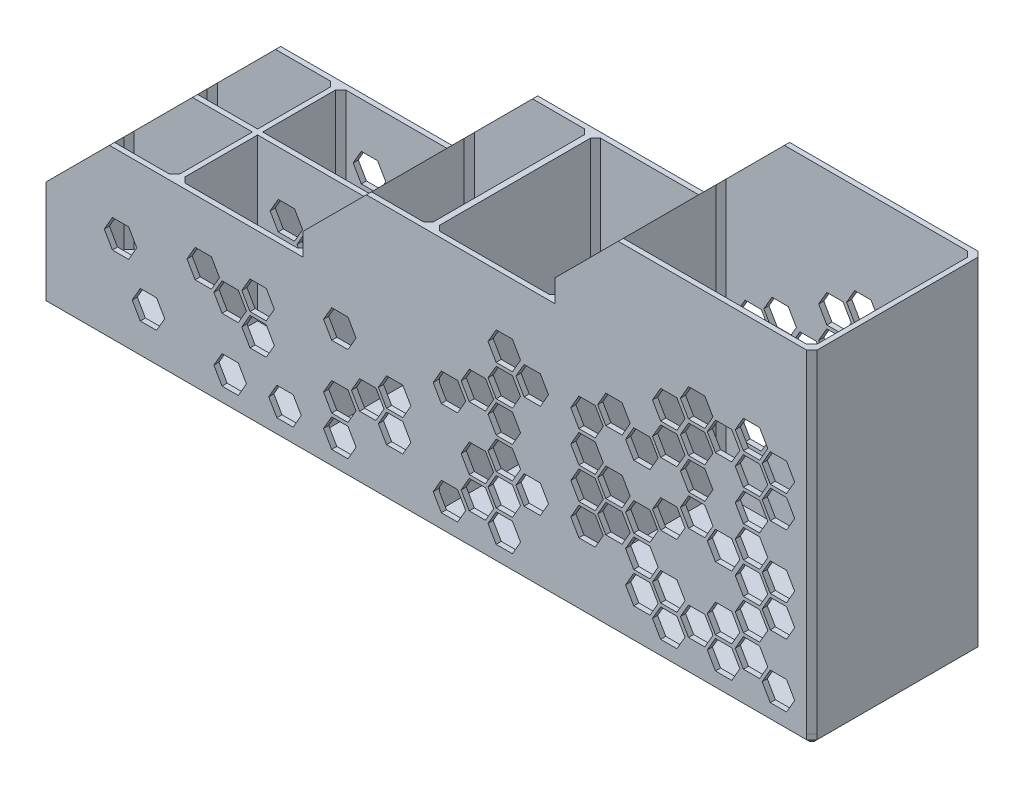
SolidWorks part; units mm, degrees
ref_plane "Front Plane" through (0, 0, 0) normal (0, 0, 1) x (1, 0, 0)
ref_plane "Top Plane" through (0, 0, 0) normal (0, 1, 0) x (1, 0, 0)
ref_plane "Right Plane" through (0, 0, 0) normal (1, 0, 0) x (0, 0, -1)
sketch "Sketch2" plane through (0, 0, 0) normal (0, 1, 0) x (1, 0, 0)
  line L0 (-36, -23.5) -> (36, -23.5)
  line L1 (-111, 25) -> (111, 25)
  line L2 (-112.5, 23.5) -> (-112.5, -23.5)
  line L3 (-111, -25) -> (111, -25)
  line L4 (112.5, 23.5) -> (112.5, -23.5)
  line L5 (-112.5, 25) -> (112.5, -25) construction
  line L6 (-112.5, -25) -> (112.5, 25) construction
  line L7 (-109.5, -23.5) -> (-39, -23.5)
  line L8 (-111, -22) -> (-111, 22)
  line L9 (-109.5, 23.5) -> (-39, 23.5)
  line L10 (111, -22) -> (111, 22)
  line L11 (-111, -23.5) -> (111, 23.5) construction
  line L12 (-111, 23.5) -> (111, -23.5) construction
  line L13 (-36, 23.5) -> (36, 23.5)
  line L14 (-37.5, 22) -> (-37.5, -22)
  line L15 (-36, -23.5) -> (36, -23.5)
  line L16 (37.5, 22) -> (37.5, -22)
  line L17 (-36, 22.56) -> (36, -22.56) construction
  line L18 (-36, -22.56) -> (36, 22.56) construction
  line L19 (-34.5, 23.5) -> (34.5, 23.5)
  line L20 (-36, 22) -> (-36, -22)
  line L21 (-34.5, -23.5) -> (34.5, -23.5)
  line L22 (36, 22) -> (36, -22)
  line L23 (-36, 23.5) -> (36, -23.5) construction
  line L24 (-36, -23.5) -> (36, 23.5) construction
  line L25 (-36, 23.5) -> (36, 23.5)
  line L26 (39, 23.5) -> (109.5, 23.5)
  line L27 (39, -23.5) -> (109.5, -23.5)
  line L28 (-111, 22) -> (-109.5, 23.5)
  line L29 (-111, -22) -> (-109.5, -23.5)
  line L30 (-37.5, -22) -> (-39, -23.5)
  line L31 (-36, -22) -> (-34.5, -23.5)
  line L32 (-36, 22) -> (-34.5, 23.5)
  line L33 (-39, 23.5) -> (-37.5, 22)
  line L34 (34.5, 23.5) -> (36, 22)
  line L35 (37.5, 22) -> (39, 23.5)
  line L36 (34.5, -23.5) -> (36, -22)
  line L37 (37.5, -22) -> (39, -23.5)
  line L38 (109.5, 23.5) -> (111, 22)
  line L39 (109.5, -23.5) -> (111, -22)
  line L40 (-112.5, -23.5) -> (-111, -25)
  line L41 (111, -25) -> (112.5, -23.5)
  line L42 (111, 25) -> (112.5, 23.5)
  line L43 (-112.5, 23.5) -> (-111, 25)
  point P0 (0, 0)
  point P5 (0, 0)
  point P11 (0, 0)
  point P12 (37.5, -23.5)
  point P13 (-37.5, 23.5)
  point P14 (-37.5, -23.5)
  point P15 (37.5, 23.5)
  point P16 (0, 0)
  dimension "D1" = 50
  dimension "D2" = 225
  dimension "D3" = 222
extrude "Boss-Extrude1" add sketch "Sketch2" along normal blind 100 contours L4 L1 L2 L3 L27 L16 L26 L10 L9 L14 L7 L8 L13 L22 L0 L20
sketch "Sketch7" plane through (0, 0, 25) normal (0, 0, 1) x (1, 0, 0)
  line L0 (112.5, 100) -> (112.5, 0) construction
  line L1 (-112.5, 0) -> (112.5, 0)
  line L2 (-112.5, 0) -> (-112.5, 3)
  line L3 (-112.5, 3) -> (112.5, 3)
  line L4 (112.5, 0) -> (112.5, 3)
  dimension "D1" = 3
extrude "Boss-Extrude3" add sketch "Sketch7" against normal up to surface (50 mm away) up to face at (0, 50, -25)
sketch "Sketch3" plane through (0, 100, 0) normal (0, 1, 0) x (1, 0, 0)
  line L0 (-37.5, 22) -> (-37.5, -22) construction
  line L2 (-109.5, -23.5) -> (-39, -23.5) construction
  line L3 (-111, 0.75) -> (-75, 0.75)
  line L4 (-75, 23.5) -> (-73.5, 23.5)
  line L5 (-75, 23.5) -> (-75, 0.75)
  line L6 (-75, -23.5) -> (-73.5, -23.5)
  line L7 (-73.5, 23.5) -> (-73.5, 0.75)
  line L8 (-111, 0.75) -> (-111, -0.75)
  line L9 (-111, -0.75) -> (-75, -0.75)
  line L10 (-37.5, 0.75) -> (-37.5, -0.75)
  line L11 (-34.5, -23.5) -> (34.5, -23.5) construction
  line L13 (-73.5, -0.75) -> (-37.5, -0.75)
  line L14 (-73.5, -0.75) -> (-73.5, -23.5)
  line L16 (-75, -0.75) -> (-75, -23.5)
  line L17 (-73.5, 0.75) -> (-37.5, 0.75)
  line L18 (-0.8781, 23.5) -> (0.8781, 23.5)
  line L19 (-0.8781, 23.5) -> (-0.8781, -23.5)
  line L20 (-0.8781, -23.5) -> (0.8781, -23.5)
  line L21 (0.8781, 23.5) -> (0.8781, -23.5)
  line L22 (-0.8781, 23.5) -> (0.8781, -23.5) construction
  line L23 (-0.8781, -23.5) -> (0.8781, 23.5) construction
  point P0 (-74.25, 0)
  point P6 (-74.25, 0)
  point P14 (0, 0)
  dimension "D1" = 1.5
extrude "Boss-Extrude2" add sketch "Sketch3" against normal up to surface (100 mm away) up to face at (0, 0, 0)
sketch "Sketch5" plane through (0, 100, 0) normal (0, 1, 0) x (1, 0, 0)
  line L0 (-111, 25) -> (111, 25) construction
  line L1 (-37.5, 25) -> (-112.5, 25)
  line L2 (-37.5, 25) -> (-37.5, -25)
  line L3 (-37.5, -25) -> (-112.5, -25)
  line L4 (-112.5, 25) -> (-112.5, -25)
extrude "Cut-Extrude1" cut sketch "Sketch5" against normal blind 50
sketch "Sketch6" plane through (0, 100, 0) normal (0, 1, 0) x (1, 0, 0)
  line L0 (-37.5, -25) -> (111, -25) construction
  line L1 (36, -25) -> (-37.5, -25)
  line L2 (36, -25) -> (36, 25)
  line L3 (36, 25) -> (-37.5, 25)
  line L4 (-37.5, -25) -> (-37.5, 25)
extrude "Cut-Extrude2" cut sketch "Sketch6" against normal blind 25
chamfer "Chamfer1" distance 1.5 angle 45 16 edges at (-37.5, 26.5, 0.75) (-73.5, 26.5, 23.5) (-75, 26.5, 23.5) (-111, 26.5, 0.75) (-111, 26.5, -0.75) (-75, 26.5, -23.5) (-73.5, 26.5, -23.5) (-37.5, 26.5, -0.75) (0.8781, 39, -23.5) (0.8781, 39, 23.5) (-0.8781, 39, 23.5) (-0.8781, 39, -23.5) (-37.5, 62.5, 25) (-37.5, 62.5, -25) (36, 87.5, -25) (36, 87.5, 25)
chamfer "Chamfer2" distance 1.5 angle 45 4 edges at (112.5, 1.5, 25) (112.5, 1.5, -25) (-112.5, 1.5, -25) (-112.5, 1.5, 25)
chamfer "Chamfer3" distance 1.5 angle 45 8 edges at (111.75, 0, -24.25) (0, 0, -25) (-111.75, 0, -24.25) (-112.5, 0, 0) (-111.75, 0, 24.25) (0, 0, 25) (111.75, 0, 24.25) (112.5, 0, 0)
chamfer "Chamfer4" distance 20 angle 45 3 edges at (36, 100, 0) (-112.5, 50, 0) (-37.5, 75, 0)
sketch "Sketch8" plane through (0, 0, 25) normal (0, 0, 1) x (1, 0, 0)
  line L0 (91.4988, 9.7004) -> (89.1233, 13.8147)
  line L1 (107.4988, 9.7004) -> (105.1233, 13.8147)
  line L2 (105.1233, 13.8147) -> (100.3725, 13.8147)
  line L3 (100.3725, 13.8147) -> (97.9971, 9.7004)
  line L4 (97.9971, 9.7004) -> (100.3725, 5.5861)
  line L5 (100.3725, 5.5861) -> (105.1233, 5.5861)
  line L6 (105.1233, 5.5861) -> (107.4988, 9.7004)
  line L7 (89.1233, 13.8147) -> (84.3725, 13.8147)
  line L8 (84.3725, 13.8147) -> (81.9971, 9.7004)
  line L9 (81.9971, 9.7004) -> (84.3725, 5.5861)
  line L10 (84.3725, 5.5861) -> (89.1233, 5.5861)
  line L11 (89.1233, 5.5861) -> (91.4988, 9.7004)
  line L16 (99.6456, 14.2344) -> (97.2702, 18.3488)
  line L17 (97.2702, 18.3488) -> (92.5194, 18.3488)
  line L18 (92.5194, 18.3488) -> (90.1439, 14.2344)
  line L19 (90.1439, 14.2344) -> (92.5194, 10.1201)
  line L20 (92.5194, 10.1201) -> (97.2702, 10.1201)
  line L21 (97.2702, 10.1201) -> (99.6456, 14.2344)
  line L22 (83.6456, 14.2344) -> (81.2702, 18.3488)
  line L23 (81.2702, 18.3488) -> (76.5194, 18.3488)
  line L24 (76.5194, 18.3488) -> (74.1439, 14.2344)
  line L25 (74.1439, 14.2344) -> (76.5194, 10.1201)
  line L26 (76.5194, 10.1201) -> (81.2702, 10.1201)
  line L27 (81.2702, 10.1201) -> (83.6456, 14.2344)
  line L28 (67.6456, 14.2344) -> (65.2702, 18.3488)
  line L29 (65.2702, 18.3488) -> (60.5194, 18.3488)
  line L30 (60.5194, 18.3488) -> (58.1439, 14.2344)
  line L31 (58.1439, 14.2344) -> (60.5194, 10.1201)
  line L32 (60.5194, 10.1201) -> (65.2702, 10.1201)
  line L33 (65.2702, 10.1201) -> (67.6456, 14.2344)
  line L46 (19.6456, 14.2344) -> (17.2702, 18.3488)
  line L47 (17.2702, 18.3488) -> (12.5194, 18.3488)
  line L48 (12.5194, 18.3488) -> (10.1439, 14.2344)
  line L49 (10.1439, 14.2344) -> (12.5194, 10.1201)
  line L50 (12.5194, 10.1201) -> (17.2702, 10.1201)
  line L51 (17.2702, 10.1201) -> (19.6456, 14.2344)
  line L82 (-76.3544, 14.2344) -> (-78.7298, 18.3488)
  line L83 (-78.7298, 18.3488) -> (-83.4806, 18.3488)
  line L84 (-83.4806, 18.3488) -> (-85.8561, 14.2344)
  line L85 (-85.8561, 14.2344) -> (-83.4806, 10.1201)
  line L86 (-83.4806, 10.1201) -> (-78.7298, 10.1201)
  line L87 (-78.7298, 10.1201) -> (-76.3544, 14.2344)
  line L88 (75.4988, 9.7004) -> (73.1233, 13.8147)
  line L89 (73.1233, 13.8147) -> (68.3725, 13.8147)
  line L90 (68.3725, 13.8147) -> (65.9971, 9.7004)
  line L91 (65.9971, 9.7004) -> (68.3725, 5.5861)
  line L92 (68.3725, 5.5861) -> (73.1233, 5.5861)
  line L93 (73.1233, 5.5861) -> (75.4988, 9.7004)
  line L106 (27.4988, 9.7004) -> (25.1233, 13.8147)
  line L107 (25.1233, 13.8147) -> (20.3725, 13.8147)
  line L108 (20.3725, 13.8147) -> (17.9971, 9.7004)
  line L109 (17.9971, 9.7004) -> (20.3725, 5.5861)
  line L110 (20.3725, 5.5861) -> (25.1233, 5.5861)
  line L111 (25.1233, 5.5861) -> (27.4988, 9.7004)
  line L112 (11.4988, 9.7004) -> (9.1233, 13.8147)
  line L113 (9.1233, 13.8147) -> (4.3725, 13.8147)
  line L114 (4.3725, 13.8147) -> (1.9971, 9.7004)
  line L115 (1.9971, 9.7004) -> (4.3725, 5.5861)
  line L116 (4.3725, 5.5861) -> (9.1233, 5.5861)
  line L117 (9.1233, 5.5861) -> (11.4988, 9.7004)
  line L124 (-20.5012, 9.7004) -> (-22.8767, 13.8147)
  line L125 (-22.8767, 13.8147) -> (-27.6275, 13.8147)
  line L126 (-27.6275, 13.8147) -> (-30.0029, 9.7004)
  line L127 (-30.0029, 9.7004) -> (-27.6275, 5.5861)
  line L128 (-27.6275, 5.5861) -> (-22.8767, 5.5861)
  line L129 (-22.8767, 5.5861) -> (-20.5012, 9.7004)
  line L130 (-36.5012, 9.7004) -> (-38.8767, 13.8147)
  line L131 (-38.8767, 13.8147) -> (-43.6275, 13.8147)
  line L132 (-43.6275, 13.8147) -> (-46.0029, 9.7004)
  line L133 (-46.0029, 9.7004) -> (-43.6275, 5.5861)
  line L134 (-43.6275, 5.5861) -> (-38.8767, 5.5861)
  line L135 (-38.8767, 5.5861) -> (-36.5012, 9.7004)
  line L136 (-52.5012, 9.7004) -> (-54.8767, 13.8147)
  line L137 (-54.8767, 13.8147) -> (-59.6275, 13.8147)
  line L138 (-59.6275, 13.8147) -> (-62.0029, 9.7004)
  line L139 (-62.0029, 9.7004) -> (-59.6275, 5.5861)
  line L140 (-59.6275, 5.5861) -> (-54.8767, 5.5861)
  line L141 (-54.8767, 5.5861) -> (-52.5012, 9.7004)
  line L154 (75.4988, 18.9004) -> (73.1233, 23.0147)
  line L155 (73.1233, 23.0147) -> (68.3725, 23.0147)
  line L156 (68.3725, 23.0147) -> (65.9971, 18.9004)
  line L157 (65.9971, 18.9004) -> (68.3725, 14.7861)
  line L158 (68.3725, 14.7861) -> (73.1233, 14.7861)
  line L159 (73.1233, 14.7861) -> (75.4988, 18.9004)
  line L178 (27.4988, 18.9004) -> (25.1233, 23.0147)
  line L179 (25.1233, 23.0147) -> (20.3725, 23.0147)
  line L180 (20.3725, 23.0147) -> (17.9971, 18.9004)
  line L181 (17.9971, 18.9004) -> (20.3725, 14.7861)
  line L182 (20.3725, 14.7861) -> (25.1233, 14.7861)
  line L183 (25.1233, 14.7861) -> (27.4988, 18.9004)
  line L190 (-4.5012, 18.9004) -> (-6.8767, 23.0147)
  line L191 (-6.8767, 23.0147) -> (-11.6275, 23.0147)
  line L192 (-11.6275, 23.0147) -> (-14.0029, 18.9004)
  line L193 (-14.0029, 18.9004) -> (-11.6275, 14.7861)
  line L194 (-11.6275, 14.7861) -> (-6.8767, 14.7861)
  line L195 (-6.8767, 14.7861) -> (-4.5012, 18.9004)
  line L196 (91.4988, 18.9004) -> (89.1233, 23.0147)
  line L197 (89.1233, 23.0147) -> (84.3725, 23.0147)
  line L198 (84.3725, 23.0147) -> (81.9971, 18.9004)
  line L199 (81.9971, 18.9004) -> (84.3725, 14.7861)
  line L200 (84.3725, 14.7861) -> (89.1233, 14.7861)
  line L201 (89.1233, 14.7861) -> (91.4988, 18.9004)
  line L216 (-27.6275, 23.0147) -> (-30.0029, 18.9004)
  line L217 (-20.5012, 18.9004) -> (-22.8767, 23.0147)
  line L218 (-22.8767, 23.0147) -> (-27.6275, 23.0147)
  line L219 (-30.0029, 18.9004) -> (-27.6275, 14.7861)
  line L220 (-27.6275, 14.7861) -> (-22.8767, 14.7861)
  line L221 (-22.8767, 14.7861) -> (-20.5012, 18.9004)
  line L238 (107.4988, 28.1004) -> (105.1233, 32.2147)
  line L239 (105.1233, 32.2147) -> (100.3725, 32.2147)
  line L240 (100.3725, 32.2147) -> (97.9971, 28.1004)
  line L241 (97.9971, 28.1004) -> (100.3725, 23.9861)
  line L242 (100.3725, 23.9861) -> (105.1233, 23.9861)
  line L243 (105.1233, 23.9861) -> (107.4988, 28.1004)
  line L244 (59.4988, 28.1004) -> (57.1233, 32.2147)
  line L245 (57.1233, 32.2147) -> (52.3725, 32.2147)
  line L246 (52.3725, 32.2147) -> (49.9971, 28.1004)
  line L247 (49.9971, 28.1004) -> (52.3725, 23.9861)
  line L248 (52.3725, 23.9861) -> (57.1233, 23.9861)
  line L249 (57.1233, 23.9861) -> (59.4988, 28.1004)
  line L256 (27.4988, 28.1004) -> (25.1233, 32.2147)
  line L257 (25.1233, 32.2147) -> (20.3725, 32.2147)
  line L258 (20.3725, 32.2147) -> (17.9971, 28.1004)
  line L259 (17.9971, 28.1004) -> (20.3725, 23.9861)
  line L260 (20.3725, 23.9861) -> (25.1233, 23.9861)
  line L261 (25.1233, 23.9861) -> (27.4988, 28.1004)
  line L268 (-4.5012, 28.1004) -> (-6.8767, 32.2147)
  line L269 (-6.8767, 32.2147) -> (-11.6275, 32.2147)
  line L270 (-11.6275, 32.2147) -> (-14.0029, 28.1004)
  line L271 (-14.0029, 28.1004) -> (-11.6275, 23.9861)
  line L272 (-11.6275, 23.9861) -> (-6.8767, 23.9861)
  line L273 (-6.8767, 23.9861) -> (-4.5012, 28.1004)
  line L280 (-84.5012, 28.1004) -> (-86.8767, 32.2147)
  line L281 (-86.8767, 32.2147) -> (-91.6275, 32.2147)
  line L282 (-91.6275, 32.2147) -> (-94.0029, 28.1004)
  line L283 (-94.0029, 28.1004) -> (-91.6275, 23.9861)
  line L284 (-91.6275, 23.9861) -> (-86.8767, 23.9861)
  line L285 (-86.8767, 23.9861) -> (-84.5012, 28.1004)
  line L292 (-59.6275, 32.2147) -> (-62.0029, 28.1004)
  line L305 (-52.5012, 28.1004) -> (-54.8767, 32.2147)
  line L306 (-54.8767, 32.2147) -> (-59.6275, 32.2147)
  line L307 (-62.0029, 28.1004) -> (-59.6275, 23.9861)
  line L308 (-59.6275, 23.9861) -> (-54.8767, 23.9861)
  line L309 (-54.8767, 23.9861) -> (-52.5012, 28.1004)
  line L310 (75.4988, 37.3004) -> (73.1233, 41.4147)
  line L311 (73.1233, 41.4147) -> (68.3725, 41.4147)
  line L312 (68.3725, 41.4147) -> (65.9971, 37.3004)
  line L313 (65.9971, 37.3004) -> (68.3725, 33.1861)
  line L314 (68.3725, 33.1861) -> (73.1233, 33.1861)
  line L315 (73.1233, 33.1861) -> (75.4988, 37.3004)
  line L316 (107.4988, 37.3004) -> (105.1233, 41.4147)
  line L317 (105.1233, 41.4147) -> (100.3725, 41.4147)
  line L318 (100.3725, 41.4147) -> (97.9971, 37.3004)
  line L319 (97.9971, 37.3004) -> (100.3725, 33.1861)
  line L320 (100.3725, 33.1861) -> (105.1233, 33.1861)
  line L321 (105.1233, 33.1861) -> (107.4988, 37.3004)
  line L322 (59.4988, 37.3004) -> (57.1233, 41.4147)
  line L323 (57.1233, 41.4147) -> (52.3725, 41.4147)
  line L324 (52.3725, 41.4147) -> (49.9971, 37.3004)
  line L325 (49.9971, 37.3004) -> (52.3725, 33.1861)
  line L326 (52.3725, 33.1861) -> (57.1233, 33.1861)
  line L327 (57.1233, 33.1861) -> (59.4988, 37.3004)
  line L334 (27.4988, 37.3004) -> (25.1233, 41.4147)
  line L335 (25.1233, 41.4147) -> (20.3725, 41.4147)
  line L336 (20.3725, 41.4147) -> (17.9971, 37.3004)
  line L337 (17.9971, 37.3004) -> (20.3725, 33.1861)
  line L338 (20.3725, 33.1861) -> (25.1233, 33.1861)
  line L339 (25.1233, 33.1861) -> (27.4988, 37.3004)
  line L340 (11.4988, 37.3004) -> (9.1233, 41.4147)
  line L341 (9.1233, 41.4147) -> (4.3725, 41.4147)
  line L342 (4.3725, 41.4147) -> (1.9971, 37.3004)
  line L343 (1.9971, 37.3004) -> (4.3725, 33.1861)
  line L344 (4.3725, 33.1861) -> (9.1233, 33.1861)
  line L345 (9.1233, 33.1861) -> (11.4988, 37.3004)
  line L352 (91.4988, 37.3004) -> (89.1233, 41.4147)
  line L353 (89.1233, 41.4147) -> (84.3725, 41.4147)
  line L354 (84.3725, 41.4147) -> (81.9971, 37.3004)
  line L355 (81.9971, 37.3004) -> (84.3725, 33.1861)
  line L356 (84.3725, 33.1861) -> (89.1233, 33.1861)
  line L357 (89.1233, 33.1861) -> (91.4988, 37.3004)
  line L372 (-27.6275, 41.4147) -> (-30.0029, 37.3004)
  line L373 (-20.5012, 37.3004) -> (-22.8767, 41.4147)
  line L374 (-22.8767, 41.4147) -> (-27.6275, 41.4147)
  line L375 (-30.0029, 37.3004) -> (-27.6275, 33.1861)
  line L376 (-27.6275, 33.1861) -> (-22.8767, 33.1861)
  line L377 (-22.8767, 33.1861) -> (-20.5012, 37.3004)
  line L412 (27.4988, 46.5004) -> (25.1233, 50.6147)
  line L413 (25.1233, 50.6147) -> (20.3725, 50.6147)
  line L414 (20.3725, 50.6147) -> (17.9971, 46.5004)
  line L415 (17.9971, 46.5004) -> (20.3725, 42.3861)
  line L416 (20.3725, 42.3861) -> (25.1233, 42.3861)
  line L417 (25.1233, 42.3861) -> (27.4988, 46.5004)
  line L466 (75.4988, 55.7004) -> (73.1233, 59.8147)
  line L467 (73.1233, 59.8147) -> (68.3725, 59.8147)
  line L468 (68.3725, 59.8147) -> (65.9971, 55.7004)
  line L469 (65.9971, 55.7004) -> (68.3725, 51.5861)
  line L470 (68.3725, 51.5861) -> (73.1233, 51.5861)
  line L471 (73.1233, 51.5861) -> (75.4988, 55.7004)
  line L472 (107.4988, 55.7004) -> (105.1233, 59.8147)
  line L473 (105.1233, 59.8147) -> (100.3725, 59.8147)
  line L474 (100.3725, 59.8147) -> (97.9971, 55.7004)
  line L475 (97.9971, 55.7004) -> (100.3725, 51.5861)
  line L476 (100.3725, 51.5861) -> (105.1233, 51.5861)
  line L477 (105.1233, 51.5861) -> (107.4988, 55.7004)
  line L478 (59.4988, 55.7004) -> (57.1233, 59.8147)
  line L479 (57.1233, 59.8147) -> (52.3725, 59.8147)
  line L480 (52.3725, 59.8147) -> (49.9971, 55.7004)
  line L481 (49.9971, 55.7004) -> (52.3725, 51.5861)
  line L482 (52.3725, 51.5861) -> (57.1233, 51.5861)
  line L483 (57.1233, 51.5861) -> (59.4988, 55.7004)
  line L490 (27.4988, 55.7004) -> (25.1233, 59.8147)
  line L491 (25.1233, 59.8147) -> (20.3725, 59.8147)
  line L492 (20.3725, 59.8147) -> (17.9971, 55.7004)
  line L493 (17.9971, 55.7004) -> (20.3725, 51.5861)
  line L494 (20.3725, 51.5861) -> (25.1233, 51.5861)
  line L495 (25.1233, 51.5861) -> (27.4988, 55.7004)
  line L544 (75.4988, 64.9004) -> (73.1233, 69.0147)
  line L545 (73.1233, 69.0147) -> (68.3725, 69.0147)
  line L546 (68.3725, 69.0147) -> (65.9971, 64.9004)
  line L547 (65.9971, 64.9004) -> (68.3725, 60.7861)
  line L548 (68.3725, 60.7861) -> (73.1233, 60.7861)
  line L549 (73.1233, 60.7861) -> (75.4988, 64.9004)
  line L550 (107.4988, 64.9004) -> (105.1233, 69.0147)
  line L551 (105.1233, 69.0147) -> (100.3725, 69.0147)
  line L552 (100.3725, 69.0147) -> (97.9971, 64.9004)
  line L553 (97.9971, 64.9004) -> (100.3725, 60.7861)
  line L554 (100.3725, 60.7861) -> (105.1233, 60.7861)
  line L555 (105.1233, 60.7861) -> (107.4988, 64.9004)
  line L586 (91.4988, 64.9004) -> (89.1233, 69.0147)
  line L587 (89.1233, 69.0147) -> (84.3725, 69.0147)
  line L588 (84.3725, 69.0147) -> (81.9971, 64.9004)
  line L589 (81.9971, 64.9004) -> (84.3725, 60.7861)
  line L590 (84.3725, 60.7861) -> (89.1233, 60.7861)
  line L591 (89.1233, 60.7861) -> (91.4988, 64.9004)
  line L634 (-44.3544, 23.4344) -> (-46.7298, 27.5488)
  line L635 (-46.7298, 27.5488) -> (-51.4806, 27.5488)
  line L636 (-51.4806, 27.5488) -> (-53.8561, 23.4344)
  line L637 (-53.8561, 23.4344) -> (-51.4806, 19.3201)
  line L638 (-51.4806, 19.3201) -> (-46.7298, 19.3201)
  line L639 (-46.7298, 19.3201) -> (-44.3544, 23.4344)
  line L646 (-12.3544, 23.4344) -> (-14.7298, 27.5488)
  line L647 (-14.7298, 27.5488) -> (-19.4806, 27.5488)
  line L648 (-19.4806, 27.5488) -> (-21.8561, 23.4344)
  line L649 (-21.8561, 23.4344) -> (-19.4806, 19.3201)
  line L650 (-19.4806, 19.3201) -> (-14.7298, 19.3201)
  line L651 (-14.7298, 19.3201) -> (-12.3544, 23.4344)
  line L658 (19.6456, 23.4344) -> (17.2702, 27.5488)
  line L659 (17.2702, 27.5488) -> (12.5194, 27.5488)
  line L660 (12.5194, 27.5488) -> (10.1439, 23.4344)
  line L661 (10.1439, 23.4344) -> (12.5194, 19.3201)
  line L662 (12.5194, 19.3201) -> (17.2702, 19.3201)
  line L663 (17.2702, 19.3201) -> (19.6456, 23.4344)
  line L664 (35.6456, 23.4344) -> (33.2702, 27.5488)
  line L665 (33.2702, 27.5488) -> (28.5194, 27.5488)
  line L666 (28.5194, 27.5488) -> (26.1439, 23.4344)
  line L667 (26.1439, 23.4344) -> (28.5194, 19.3201)
  line L668 (28.5194, 19.3201) -> (33.2702, 19.3201)
  line L669 (33.2702, 19.3201) -> (35.6456, 23.4344)
  line L670 (51.6456, 23.4344) -> (49.2702, 27.5488)
  line L671 (49.2702, 27.5488) -> (44.5194, 27.5488)
  line L672 (44.5194, 27.5488) -> (42.1439, 23.4344)
  line L673 (42.1439, 23.4344) -> (44.5194, 19.3201)
  line L674 (44.5194, 19.3201) -> (49.2702, 19.3201)
  line L675 (49.2702, 19.3201) -> (51.6456, 23.4344)
  line L676 (67.6456, 23.4344) -> (65.2702, 27.5488)
  line L677 (65.2702, 27.5488) -> (60.5194, 27.5488)
  line L678 (60.5194, 27.5488) -> (58.1439, 23.4344)
  line L679 (58.1439, 23.4344) -> (60.5194, 19.3201)
  line L680 (60.5194, 19.3201) -> (65.2702, 19.3201)
  line L681 (65.2702, 19.3201) -> (67.6456, 23.4344)
  line L688 (99.6456, 23.4344) -> (97.2702, 27.5488)
  line L689 (97.2702, 27.5488) -> (92.5194, 27.5488)
  line L690 (92.5194, 27.5488) -> (90.1439, 23.4344)
  line L691 (90.1439, 23.4344) -> (92.5194, 19.3201)
  line L692 (92.5194, 19.3201) -> (97.2702, 19.3201)
  line L693 (97.2702, 19.3201) -> (99.6456, 23.4344)
  line L700 (-60.3544, 32.6344) -> (-62.7298, 36.7488)
  line L701 (-62.7298, 36.7488) -> (-67.4806, 36.7488)
  line L702 (-67.4806, 36.7488) -> (-69.8561, 32.6344)
  line L703 (-69.8561, 32.6344) -> (-67.4806, 28.5201)
  line L704 (-67.4806, 28.5201) -> (-62.7298, 28.5201)
  line L705 (-62.7298, 28.5201) -> (-60.3544, 32.6344)
  line L706 (-44.3544, 32.6344) -> (-46.7298, 36.7488)
  line L707 (-46.7298, 36.7488) -> (-51.4806, 36.7488)
  line L708 (-51.4806, 36.7488) -> (-53.8561, 32.6344)
  line L709 (-53.8561, 32.6344) -> (-51.4806, 28.5201)
  line L710 (-51.4806, 28.5201) -> (-46.7298, 28.5201)
  line L711 (-46.7298, 28.5201) -> (-44.3544, 32.6344)
  line L742 (51.6456, 32.6344) -> (49.2702, 36.7488)
  line L743 (49.2702, 36.7488) -> (44.5194, 36.7488)
  line L744 (44.5194, 36.7488) -> (42.1439, 32.6344)
  line L745 (42.1439, 32.6344) -> (44.5194, 28.5201)
  line L746 (44.5194, 28.5201) -> (49.2702, 28.5201)
  line L747 (49.2702, 28.5201) -> (51.6456, 32.6344)
  line L748 (67.6456, 32.6344) -> (65.2702, 36.7488)
  line L749 (65.2702, 36.7488) -> (60.5194, 36.7488)
  line L750 (60.5194, 36.7488) -> (58.1439, 32.6344)
  line L751 (58.1439, 32.6344) -> (60.5194, 28.5201)
  line L752 (60.5194, 28.5201) -> (65.2702, 28.5201)
  line L753 (65.2702, 28.5201) -> (67.6456, 32.6344)
  line L760 (99.6456, 32.6344) -> (97.2702, 36.7488)
  line L761 (97.2702, 36.7488) -> (92.5194, 36.7488)
  line L762 (92.5194, 36.7488) -> (90.1439, 32.6344)
  line L763 (90.1439, 32.6344) -> (92.5194, 28.5201)
  line L764 (92.5194, 28.5201) -> (97.2702, 28.5201)
  line L765 (97.2702, 28.5201) -> (99.6456, 32.6344)
  line L802 (19.6456, 41.8344) -> (17.2702, 45.9488)
  line L803 (17.2702, 45.9488) -> (12.5194, 45.9488)
  line L804 (12.5194, 45.9488) -> (10.1439, 41.8344)
  line L805 (10.1439, 41.8344) -> (12.5194, 37.7201)
  line L806 (12.5194, 37.7201) -> (17.2702, 37.7201)
  line L807 (17.2702, 37.7201) -> (19.6456, 41.8344)
  line L814 (51.6456, 41.8344) -> (49.2702, 45.9488)
  line L815 (49.2702, 45.9488) -> (44.5194, 45.9488)
  line L816 (44.5194, 45.9488) -> (42.1439, 41.8344)
  line L817 (42.1439, 41.8344) -> (44.5194, 37.7201)
  line L818 (44.5194, 37.7201) -> (49.2702, 37.7201)
  line L819 (49.2702, 37.7201) -> (51.6456, 41.8344)
  line L826 (83.6456, 41.8344) -> (81.2702, 45.9488)
  line L827 (81.2702, 45.9488) -> (76.5194, 45.9488)
  line L828 (76.5194, 45.9488) -> (74.1439, 41.8344)
  line L829 (74.1439, 41.8344) -> (76.5194, 37.7201)
  line L830 (76.5194, 37.7201) -> (81.2702, 37.7201)
  line L831 (81.2702, 37.7201) -> (83.6456, 41.8344)
  line L832 (99.6456, 41.8344) -> (97.2702, 45.9488)
  line L833 (97.2702, 45.9488) -> (92.5194, 45.9488)
  line L834 (92.5194, 45.9488) -> (90.1439, 41.8344)
  line L835 (90.1439, 41.8344) -> (92.5194, 37.7201)
  line L836 (92.5194, 37.7201) -> (97.2702, 37.7201)
  line L837 (97.2702, 37.7201) -> (99.6456, 41.8344)
  line L880 (35.6456, 51.0344) -> (33.2702, 55.1488)
  line L881 (33.2702, 55.1488) -> (28.5194, 55.1488)
  line L882 (28.5194, 55.1488) -> (26.1439, 51.0344)
  line L883 (26.1439, 51.0344) -> (28.5194, 46.9201)
  line L884 (28.5194, 46.9201) -> (33.2702, 46.9201)
  line L885 (33.2702, 46.9201) -> (35.6456, 51.0344)
  line L886 (51.6456, 51.0344) -> (49.2702, 55.1488)
  line L887 (49.2702, 55.1488) -> (44.5194, 55.1488)
  line L888 (44.5194, 55.1488) -> (42.1439, 51.0344)
  line L889 (42.1439, 51.0344) -> (44.5194, 46.9201)
  line L890 (44.5194, 46.9201) -> (49.2702, 46.9201)
  line L891 (49.2702, 46.9201) -> (51.6456, 51.0344)
  line L892 (67.6456, 51.0344) -> (65.2702, 55.1488)
  line L893 (65.2702, 55.1488) -> (60.5194, 55.1488)
  line L894 (60.5194, 55.1488) -> (58.1439, 51.0344)
  line L895 (58.1439, 51.0344) -> (60.5194, 46.9201)
  line L896 (60.5194, 46.9201) -> (65.2702, 46.9201)
  line L897 (65.2702, 46.9201) -> (67.6456, 51.0344)
  line L898 (83.6456, 51.0344) -> (81.2702, 55.1488)
  line L899 (81.2702, 55.1488) -> (76.5194, 55.1488)
  line L900 (76.5194, 55.1488) -> (74.1439, 51.0344)
  line L901 (74.1439, 51.0344) -> (76.5194, 46.9201)
  line L902 (76.5194, 46.9201) -> (81.2702, 46.9201)
  line L903 (81.2702, 46.9201) -> (83.6456, 51.0344)
  line L904 (99.6456, 51.0344) -> (97.2702, 55.1488)
  line L905 (97.2702, 55.1488) -> (92.5194, 55.1488)
  line L906 (92.5194, 55.1488) -> (90.1439, 51.0344)
  line L907 (90.1439, 51.0344) -> (92.5194, 46.9201)
  line L908 (92.5194, 46.9201) -> (97.2702, 46.9201)
  line L909 (97.2702, 46.9201) -> (99.6456, 51.0344)
  line L970 (83.6456, 60.2344) -> (81.2702, 64.3488)
  line L971 (81.2702, 64.3488) -> (76.5194, 64.3488)
  line L972 (76.5194, 64.3488) -> (74.1439, 60.2344)
  line L973 (74.1439, 60.2344) -> (76.5194, 56.1201)
  line L974 (76.5194, 56.1201) -> (81.2702, 56.1201)
  line L975 (81.2702, 56.1201) -> (83.6456, 60.2344)
  line L976 (99.6456, 60.2344) -> (97.2702, 64.3488)
  line L977 (97.2702, 64.3488) -> (92.5194, 64.3488)
  line L978 (92.5194, 64.3488) -> (90.1439, 60.2344)
  line L979 (90.1439, 60.2344) -> (92.5194, 56.1201)
  line L980 (92.5194, 56.1201) -> (97.2702, 56.1201)
  line L981 (97.2702, 56.1201) -> (99.6456, 60.2344)
  line L1042 (83.6456, 69.4344) -> (81.2702, 73.5488)
  line L1043 (81.2702, 73.5488) -> (76.5194, 73.5488)
  line L1044 (76.5194, 73.5488) -> (74.1439, 69.4344)
  line L1045 (74.1439, 69.4344) -> (76.5194, 65.3201)
  line L1046 (76.5194, 65.3201) -> (81.2702, 65.3201)
  line L1047 (81.2702, 65.3201) -> (83.6456, 69.4344)
  line L1048 (99.6456, 69.4344) -> (97.2702, 73.5488)
  line L1049 (97.2702, 73.5488) -> (92.5194, 73.5488)
  line L1050 (92.5194, 73.5488) -> (90.1439, 69.4344)
  line L1051 (90.1439, 69.4344) -> (92.5194, 65.3201)
  line L1052 (92.5194, 65.3201) -> (97.2702, 65.3201)
  line L1053 (97.2702, 65.3201) -> (99.6456, 69.4344)
  line L1060 (-59.6275, 50.6147) -> (-62.0029, 46.5004) [skipped]
  line L1061 (-36.5012, 46.5004) -> (-38.8767, 50.6147) [skipped]
  line L1062 (-27.6275, 50.6147) -> (-30.0029, 46.5004) [skipped]
  line L1063 (-20.5012, 46.5004) -> (-22.8767, 50.6147) [skipped]
  line L1064 (-22.8767, 50.6147) -> (-27.6275, 50.6147) [skipped]
  line L1065 (-38.8767, 50.6147) -> (-43.6275, 50.6147) [skipped]
  line L1066 (-43.6275, 50.6147) -> (-46.0029, 46.5004) [skipped]
  line L1067 (-52.5012, 46.5004) -> (-54.8767, 50.6147) [skipped]
  line L1068 (-54.8767, 50.6147) -> (-59.6275, 50.6147) [skipped]
  line L1081 (-59.6275, 59.8147) -> (-62.0029, 55.7004) [skipped]
  line L1082 (-36.5012, 55.7004) -> (-38.8767, 59.8147) [skipped]
  line L1083 (-27.6275, 59.8147) -> (-30.0029, 55.7004) [skipped]
  line L1084 (-20.5012, 55.7004) -> (-22.8767, 59.8147) [skipped]
  line L1085 (-22.8767, 59.8147) -> (-27.6275, 59.8147) [skipped]
  line L1086 (-30.0029, 55.7004) -> (-27.6275, 51.5861) [skipped]
  line L1087 (-27.6275, 51.5861) -> (-22.8767, 51.5861) [skipped]
  line L1088 (-22.8767, 51.5861) -> (-20.5012, 55.7004) [skipped]
  line L1089 (-38.8767, 59.8147) -> (-43.6275, 59.8147) [skipped]
  line L1090 (-43.6275, 59.8147) -> (-46.0029, 55.7004) [skipped]
  line L1091 (-46.0029, 55.7004) -> (-43.6275, 51.5861) [skipped]
  line L1092 (-43.6275, 51.5861) -> (-38.8767, 51.5861) [skipped]
  line L1093 (-38.8767, 51.5861) -> (-36.5012, 55.7004) [skipped]
  line L1094 (-52.5012, 55.7004) -> (-54.8767, 59.8147) [skipped]
  line L1095 (-54.8767, 59.8147) -> (-59.6275, 59.8147) [skipped]
  line L1096 (-62.0029, 55.7004) -> (-59.6275, 51.5861) [skipped]
  line L1097 (-59.6275, 51.5861) -> (-54.8767, 51.5861) [skipped]
  line L1098 (-54.8767, 51.5861) -> (-52.5012, 55.7004) [skipped]
  line L1111 (-59.6275, 69.0147) -> (-62.0029, 64.9004) [skipped]
  line L1112 (-36.5012, 64.9004) -> (-38.8767, 69.0147) [skipped]
  line L1113 (-27.6275, 69.0147) -> (-30.0029, 64.9004) [skipped]
  line L1114 (-20.5012, 64.9004) -> (-22.8767, 69.0147) [skipped]
  line L1115 (-22.8767, 69.0147) -> (-27.6275, 69.0147) [skipped]
  line L1116 (-30.0029, 64.9004) -> (-27.6275, 60.7861) [skipped]
  line L1117 (-27.6275, 60.7861) -> (-22.8767, 60.7861) [skipped]
  line L1118 (-22.8767, 60.7861) -> (-20.5012, 64.9004) [skipped]
  line L1119 (-38.8767, 69.0147) -> (-43.6275, 69.0147) [skipped]
  line L1120 (-43.6275, 69.0147) -> (-46.0029, 64.9004) [skipped]
  line L1121 (-46.0029, 64.9004) -> (-43.6275, 60.7861) [skipped]
  line L1122 (-43.6275, 60.7861) -> (-38.8767, 60.7861) [skipped]
  line L1123 (-38.8767, 60.7861) -> (-36.5012, 64.9004) [skipped]
  line L1124 (-52.5012, 64.9004) -> (-54.8767, 69.0147) [skipped]
  line L1125 (-54.8767, 69.0147) -> (-59.6275, 69.0147) [skipped]
  line L1126 (-62.0029, 64.9004) -> (-59.6275, 60.7861) [skipped]
  line L1127 (-59.6275, 60.7861) -> (-54.8767, 60.7861) [skipped]
  line L1128 (-54.8767, 60.7861) -> (-52.5012, 64.9004) [skipped]
  line L1129 (-78.7298, 45.9488) -> (-83.4806, 45.9488) [skipped]
  line L1133 (-76.3544, 51.0344) -> (-78.7298, 55.1488) [skipped]
  line L1134 (-78.7298, 55.1488) -> (-83.4806, 55.1488) [skipped]
  line L1135 (-83.4806, 55.1488) -> (-85.8561, 51.0344) [skipped]
  line L1136 (-85.8561, 51.0344) -> (-83.4806, 46.9201) [skipped]
  line L1137 (-83.4806, 46.9201) -> (-78.7298, 46.9201) [skipped]
  line L1138 (-78.7298, 46.9201) -> (-76.3544, 51.0344) [skipped]
  line L1157 (-76.3544, 60.2344) -> (-78.7298, 64.3488) [skipped]
  line L1158 (-78.7298, 64.3488) -> (-83.4806, 64.3488) [skipped]
  line L1159 (-83.4806, 64.3488) -> (-85.8561, 60.2344) [skipped]
  line L1160 (-85.8561, 60.2344) -> (-83.4806, 56.1201) [skipped]
  line L1161 (-83.4806, 56.1201) -> (-78.7298, 56.1201) [skipped]
  line L1162 (-78.7298, 56.1201) -> (-76.3544, 60.2344) [skipped]
  line L1181 (-76.3544, 69.4344) -> (-78.7298, 73.5488) [skipped]
  line L1182 (-78.7298, 73.5488) -> (-83.4806, 73.5488) [skipped]
  line L1183 (-83.4806, 73.5488) -> (-85.8561, 69.4344) [skipped]
  line L1184 (-85.8561, 69.4344) -> (-83.4806, 65.3201) [skipped]
  line L1185 (-83.4806, 65.3201) -> (-78.7298, 65.3201) [skipped]
  line L1186 (-78.7298, 65.3201) -> (-76.3544, 69.4344) [skipped]
  line L1207 (-83.4806, 45.9488) -> (-85.8561, 41.8344) [skipped]
  line L1209 (-85.8561, 41.8344) -> (-83.4806, 37.7201) [skipped]
  line L1210 (-83.4806, 37.7201) -> (-78.7298, 37.7201) [skipped]
  line L1211 (-78.7298, 37.7201) -> (-76.3544, 41.8344) [skipped]
  line L1212 (-76.3544, 41.8344) -> (-78.7298, 45.9488) [skipped]
  line L1220 (-62.0029, 46.5004) -> (-59.6275, 42.3861) [skipped]
  line L1221 (-59.6275, 42.3861) -> (-54.8767, 42.3861) [skipped]
  line L1223 (-54.8767, 42.3861) -> (-52.5012, 46.5004) [skipped]
  line L1229 (-46.0029, 46.5004) -> (-43.6275, 42.3861) [skipped]
  line L1230 (-43.6275, 42.3861) -> (-38.8767, 42.3861) [skipped]
  line L1232 (-38.8767, 42.3861) -> (-36.5012, 46.5004) [skipped]
  line L1234 (-30.0029, 46.5004) -> (-27.6275, 42.3861) [skipped]
  line L1236 (-27.6275, 42.3861) -> (-22.8767, 42.3861) [skipped]
  line L1237 (-22.8767, 42.3861) -> (-20.5012, 46.5004) [skipped]
  line L1240 (9.1233, 50.6147) -> (4.3725, 50.6147) [skipped]
  line L1242 (11.4988, 55.7004) -> (9.1233, 59.8147) [skipped]
  line L1243 (9.1233, 59.8147) -> (4.3725, 59.8147) [skipped]
  line L1244 (4.3725, 59.8147) -> (1.9971, 55.7004) [skipped]
  line L1245 (1.9971, 55.7004) -> (4.3725, 51.5861) [skipped]
  line L1246 (4.3725, 51.5861) -> (9.1233, 51.5861) [skipped]
  line L1247 (9.1233, 51.5861) -> (11.4988, 55.7004) [skipped]
  line L1254 (11.4988, 64.9004) -> (9.1233, 69.0147) [skipped]
  line L1255 (9.1233, 69.0147) -> (4.3725, 69.0147) [skipped]
  line L1256 (4.3725, 69.0147) -> (1.9971, 64.9004) [skipped]
  line L1257 (1.9971, 64.9004) -> (4.3725, 60.7861) [skipped]
  line L1258 (4.3725, 60.7861) -> (9.1233, 60.7861) [skipped]
  line L1259 (9.1233, 60.7861) -> (11.4988, 64.9004) [skipped]
  line L1272 (12.5194, 55.1488) -> (10.1439, 51.0344) [skipped]
  line L1285 (12.5194, 64.3488) -> (10.1439, 60.2344) [skipped]
  line L1286 (10.1439, 60.2344) -> (12.5194, 56.1201) [skipped]
  line L1299 (12.5194, 73.5488) -> (10.1439, 69.4344) [skipped]
  line L1300 (10.1439, 69.4344) -> (12.5194, 65.3201) [skipped]
  line L1311 (4.3725, 50.6147) -> (1.9971, 46.5004) [skipped]
  line L1312 (4.3725, 42.3861) -> (9.1233, 42.3861) [skipped]
  line L1313 (9.1233, 42.3861) -> (11.4988, 46.5004) [skipped]
  line L1314 (11.4988, 46.5004) -> (9.1233, 50.6147) [skipped]
  line L1315 (10.1439, 51.0344) -> (12.5194, 46.9201) [skipped]
  line L1317 (1.9971, 46.5004) -> (4.3725, 42.3861) [skipped]
  line L1318 (12.5194, 46.9201) -> (17.2702, 46.9201) [skipped]
  line L1319 (17.2702, 46.9201) -> (19.6456, 51.0344) [skipped]
  line L1320 (17.2702, 55.1488) -> (12.5194, 55.1488) [skipped]
  line L1321 (12.5194, 56.1201) -> (17.2702, 56.1201) [skipped]
  line L1322 (19.6456, 51.0344) -> (17.2702, 55.1488) [skipped]
  line L1323 (17.2702, 56.1201) -> (19.6456, 60.2344) [skipped]
  line L1324 (19.6456, 69.4344) -> (17.2702, 73.5488) [skipped]
  line L1325 (12.5194, 65.3201) -> (17.2702, 65.3201) [skipped]
  line L1326 (17.2702, 64.3488) -> (12.5194, 64.3488) [skipped]
  line L1327 (19.6456, 60.2344) -> (17.2702, 64.3488) [skipped]
  line L1328 (17.2702, 65.3201) -> (19.6456, 69.4344) [skipped]
  line L1329 (17.2702, 73.5488) -> (12.5194, 73.5488) [skipped]
  line L1330 (-19.4806, 10.1201) -> (-14.7298, 10.1201) [skipped]
  line L1331 (-21.8561, 14.2344) -> (-19.4806, 10.1201) [skipped]
  line L1332 (-19.4806, 18.3488) -> (-21.8561, 14.2344) [skipped]
  line L1333 (-14.7298, 18.3488) -> (-19.4806, 18.3488) [skipped]
  line L1334 (-12.3544, 14.2344) -> (-14.7298, 18.3488) [skipped]
  line L1335 (-14.7298, 10.1201) -> (-12.3544, 14.2344) [skipped]
  line L1354 (-76.3544, 23.4344) -> (-78.7298, 27.5488) [skipped]
  line L1355 (-85.8561, 23.4344) -> (-83.4806, 19.3201) [skipped]
  line L1356 (-83.4806, 19.3201) -> (-78.7298, 19.3201) [skipped]
  line L1357 (-78.7298, 19.3201) -> (-76.3544, 23.4344) [skipped]
  line L1358 (-78.7298, 27.5488) -> (-83.4806, 27.5488) [skipped]
  line L1359 (-83.4806, 27.5488) -> (-85.8561, 23.4344) [skipped]
  line L1360 (-86.8767, 5.5861) -> (-84.5012, 9.7004) [skipped]
  line L1361 (-91.6275, 13.8147) -> (-94.0029, 9.7004) [skipped]
  line L1362 (-94.0029, 9.7004) -> (-91.6275, 5.5861) [skipped]
  line L1363 (-91.6275, 5.5861) -> (-86.8767, 5.5861) [skipped]
  line L1364 (-84.5012, 9.7004) -> (-86.8767, 13.8147) [skipped]
  line L1365 (-86.8767, 13.8147) -> (-91.6275, 13.8147) [skipped]
  line L1366 (-83.4806, 28.5201) -> (-78.7298, 28.5201) [skipped]
  line L1367 (-78.7298, 36.7488) -> (-83.4806, 36.7488) [skipped]
  line L1368 (-83.4806, 36.7488) -> (-85.8561, 32.6344) [skipped]
  line L1369 (-85.8561, 32.6344) -> (-83.4806, 28.5201) [skipped]
  line L1370 (-78.7298, 28.5201) -> (-76.3544, 32.6344) [skipped]
  line L1371 (-76.3544, 32.6344) -> (-78.7298, 36.7488) [skipped]
  line L1372 (17.9971, 64.9004) -> (20.3725, 60.7861) [skipped]
  line L1373 (27.4988, 64.9004) -> (25.1233, 69.0147) [skipped]
  line L1377 (20.3725, 69.0147) -> (17.9971, 64.9004) [skipped]
  line L1378 (25.1233, 69.0147) -> (20.3725, 69.0147) [skipped]
  line L1380 (25.1233, 60.7861) -> (27.4988, 64.9004) [skipped]
  line L1381 (20.3725, 60.7861) -> (25.1233, 60.7861) [skipped]
  line L1408 (33.9971, 9.7004) -> (36.3725, 5.5861) [skipped]
  line L1409 (41.1233, 13.8147) -> (36.3725, 13.8147) [skipped]
  line L1411 (35.6456, 14.2344) -> (33.2702, 18.3488) [skipped]
  line L1412 (33.2702, 10.1201) -> (35.6456, 14.2344) [skipped]
  line L1413 (36.3725, 13.8147) -> (33.9971, 9.7004) [skipped]
  line L1414 (41.1233, 5.5861) -> (43.4988, 9.7004) [skipped]
  line L1415 (36.3725, 5.5861) -> (41.1233, 5.5861) [skipped]
  line L1416 (43.4988, 9.7004) -> (41.1233, 13.8147) [skipped]
  line L1417 (33.2702, 18.3488) -> (28.5194, 18.3488) [skipped]
  line L1418 (28.5194, 18.3488) -> (26.1439, 14.2344) [skipped]
  line L1419 (26.1439, 14.2344) -> (28.5194, 10.1201) [skipped]
  line L1420 (28.5194, 10.1201) -> (33.2702, 10.1201) [skipped]
  line L1422 (-38.8767, 23.9861) -> (-36.5012, 28.1004) [skipped]
  line L1423 (-43.6275, 23.9861) -> (-38.8767, 23.9861) [skipped]
  line L1424 (-38.8767, 23.0147) -> (-43.6275, 23.0147) [skipped]
  line L1425 (-36.5012, 18.9004) -> (-38.8767, 23.0147) [skipped]
  line L1427 (-38.8767, 14.7861) -> (-36.5012, 18.9004) [skipped]
  line L1431 (-36.5012, 28.1004) -> (-38.8767, 32.2147) [skipped]
  line L1432 (-38.8767, 32.2147) -> (-43.6275, 32.2147) [skipped]
  line L1433 (-43.6275, 32.2147) -> (-46.0029, 28.1004) [skipped]
  line L1434 (-46.0029, 28.1004) -> (-43.6275, 23.9861) [skipped]
  line L1435 (-43.6275, 23.0147) -> (-46.0029, 18.9004) [skipped]
  line L1436 (-46.0029, 18.9004) -> (-43.6275, 14.7861) [skipped]
  line L1437 (-43.6275, 14.7861) -> (-38.8767, 14.7861) [skipped]
  line L1438 (-51.4806, 18.3488) -> (-53.8561, 14.2344) [skipped]
  line L1439 (-53.8561, 14.2344) -> (-51.4806, 10.1201) [skipped]
  line L1440 (-46.7298, 10.1201) -> (-44.3544, 14.2344) [skipped]
  line L1441 (-51.4806, 10.1201) -> (-46.7298, 10.1201) [skipped]
  line L1442 (-44.3544, 14.2344) -> (-46.7298, 18.3488) [skipped]
  line L1443 (-46.7298, 18.3488) -> (-51.4806, 18.3488) [skipped]
  line L1444 (81.9971, 28.1004) -> (84.3725, 23.9861) [skipped]
  line L1445 (83.6456, 23.4344) -> (81.2702, 27.5488) [skipped]
  line L1446 (81.2702, 27.5488) -> (76.5194, 27.5488) [skipped]
  line L1447 (76.5194, 28.5201) -> (81.2702, 28.5201) [skipped]
  line L1448 (74.1439, 32.6344) -> (76.5194, 28.5201) [skipped]
  line L1449 (75.4988, 28.1004) -> (73.1233, 32.2147) [skipped]
  line L1450 (73.1233, 23.9861) -> (75.4988, 28.1004) [skipped]
  line L1451 (76.5194, 27.5488) -> (74.1439, 23.4344) [skipped]
  line L1452 (68.3725, 23.9861) -> (73.1233, 23.9861) [skipped]
  line L1453 (74.1439, 23.4344) -> (76.5194, 19.3201) [skipped]
  line L1454 (81.2702, 19.3201) -> (83.6456, 23.4344) [skipped]
  line L1455 (76.5194, 19.3201) -> (81.2702, 19.3201) [skipped]
  line L1456 (84.3725, 23.9861) -> (89.1233, 23.9861) [skipped]
  line L1457 (84.3725, 32.2147) -> (81.9971, 28.1004) [skipped]
  line L1458 (81.2702, 28.5201) -> (83.6456, 32.6344) [skipped]
  line L1459 (89.1233, 23.9861) -> (91.4988, 28.1004) [skipped]
  line L1460 (91.4988, 28.1004) -> (89.1233, 32.2147) [skipped]
  line L1461 (89.1233, 32.2147) -> (84.3725, 32.2147) [skipped]
  line L1462 (83.6456, 32.6344) -> (81.2702, 36.7488) [skipped]
  line L1463 (81.2702, 36.7488) -> (76.5194, 36.7488) [skipped]
  line L1464 (76.5194, 36.7488) -> (74.1439, 32.6344) [skipped]
  line L1465 (73.1233, 32.2147) -> (68.3725, 32.2147) [skipped]
  line L1466 (68.3725, 32.2147) -> (65.9971, 28.1004) [skipped]
  line L1467 (65.9971, 28.1004) -> (68.3725, 23.9861) [skipped]
  line L1469 (60.5194, 45.9488) -> (58.1439, 41.8344) [skipped]
  line L1470 (65.2702, 45.9488) -> (60.5194, 45.9488) [skipped]
  line L1475 (58.1439, 41.8344) -> (60.5194, 37.7201) [skipped]
  line L1476 (60.5194, 37.7201) -> (65.2702, 37.7201) [skipped]
  line L1477 (65.2702, 37.7201) -> (67.6456, 41.8344) [skipped]
  line L1478 (67.6456, 41.8344) -> (65.2702, 45.9488) [skipped]
  line L1498 (10.1439, 32.6344) -> (12.5194, 28.5201) [skipped]
  line L1499 (17.2702, 28.5201) -> (19.6456, 32.6344) [skipped]
  line L1500 (12.5194, 28.5201) -> (17.2702, 28.5201) [skipped]
  line L1501 (19.6456, 32.6344) -> (17.2702, 36.7488) [skipped]
  line L1502 (17.2702, 36.7488) -> (12.5194, 36.7488) [skipped]
  line L1503 (12.5194, 36.7488) -> (10.1439, 32.6344) [skipped]
  line L1504 (11.4988, 28.1004) -> (9.1233, 32.2147) [skipped]
  line L1505 (1.9971, 28.1004) -> (4.3725, 23.9861) [skipped]
  line L1506 (4.3725, 23.9861) -> (9.1233, 23.9861) [skipped]
  line L1507 (9.1233, 23.9861) -> (11.4988, 28.1004) [skipped]
  line L1508 (9.1233, 32.2147) -> (4.3725, 32.2147) [skipped]
  line L1509 (4.3725, 32.2147) -> (1.9971, 28.1004) [skipped]
  line L1510 (84.3725, 51.5861) -> (89.1233, 51.5861) [skipped]
  line L1511 (89.1233, 50.6147) -> (84.3725, 50.6147) [skipped]
  line L1512 (91.4988, 46.5004) -> (89.1233, 50.6147) [skipped]
  line L1513 (89.1233, 42.3861) -> (91.4988, 46.5004) [skipped]
  line L1514 (84.3725, 42.3861) -> (89.1233, 42.3861) [skipped]
  line L1515 (81.9971, 46.5004) -> (84.3725, 42.3861) [skipped]
  line L1516 (84.3725, 50.6147) -> (81.9971, 46.5004) [skipped]
  line L1517 (81.9971, 55.7004) -> (84.3725, 51.5861) [skipped]
  line L1518 (89.1233, 51.5861) -> (91.4988, 55.7004) [skipped]
  line L1519 (91.4988, 55.7004) -> (89.1233, 59.8147) [skipped]
  line L1520 (89.1233, 59.8147) -> (84.3725, 59.8147) [skipped]
  line L1521 (84.3725, 59.8147) -> (81.9971, 55.7004) [skipped]
  line L1522 (107.4988, 18.9004) -> (105.1233, 23.0147) [skipped]
  line L1523 (100.3725, 23.0147) -> (97.9971, 18.9004) [skipped]
  line L1524 (97.9971, 18.9004) -> (100.3725, 14.7861) [skipped]
  line L1525 (100.3725, 14.7861) -> (105.1233, 14.7861) [skipped]
  line L1526 (105.1233, 14.7861) -> (107.4988, 18.9004) [skipped]
  line L1527 (105.1233, 23.0147) -> (100.3725, 23.0147) [skipped]
  line L1534 (-52.5012, 37.3004) -> (-54.8767, 41.4147) [skipped]
  line L1535 (-59.6275, 41.4147) -> (-62.0029, 37.3004) [skipped]
  line L1536 (-54.8767, 41.4147) -> (-59.6275, 41.4147) [skipped]
  line L1537 (-62.0029, 37.3004) -> (-59.6275, 33.1861) [skipped]
  line L1538 (-54.8767, 33.1861) -> (-52.5012, 37.3004) [skipped]
  line L1539 (-59.6275, 33.1861) -> (-54.8767, 33.1861) [skipped]
  line L1540 (-6.8767, 5.5861) -> (-4.5012, 9.7004) [skipped]
  line L1541 (-11.6275, 13.8147) -> (-14.0029, 9.7004) [skipped]
  line L1542 (-14.0029, 9.7004) -> (-11.6275, 5.5861) [skipped]
  line L1543 (-11.6275, 5.5861) -> (-6.8767, 5.5861) [skipped]
  line L1544 (-4.5012, 9.7004) -> (-6.8767, 13.8147) [skipped]
  line L1545 (-6.8767, 13.8147) -> (-11.6275, 13.8147) [skipped]
  line L1546 (68.3725, 50.6147) -> (65.9971, 46.5004) [skipped]
  line L1547 (65.9971, 46.5004) -> (68.3725, 42.3861) [skipped]
  line L1548 (73.1233, 42.3861) -> (75.4988, 46.5004) [skipped]
  line L1549 (75.4988, 46.5004) -> (73.1233, 50.6147) [skipped]
  line L1550 (73.1233, 50.6147) -> (68.3725, 50.6147) [skipped]
  line L1551 (68.3725, 42.3861) -> (73.1233, 42.3861) [skipped]
  line L1552 (67.6456, 69.4344) -> (65.2702, 73.5488) [skipped]
  line L1553 (58.1439, 69.4344) -> (60.5194, 65.3201) [skipped]
  line L1554 (65.2702, 65.3201) -> (67.6456, 69.4344) [skipped]
  line L1555 (60.5194, 65.3201) -> (65.2702, 65.3201) [skipped]
  line L1556 (60.5194, 73.5488) -> (58.1439, 69.4344) [skipped]
  line L1557 (65.2702, 73.5488) -> (60.5194, 73.5488) [skipped]
  line L1558 (-36.5012, 37.3004) -> (-38.8767, 41.4147) [skipped]
  line L1559 (-43.6275, 41.4147) -> (-46.0029, 37.3004) [skipped]
  line L1560 (-46.0029, 37.3004) -> (-43.6275, 33.1861) [skipped]
  line L1561 (-43.6275, 33.1861) -> (-38.8767, 33.1861) [skipped]
  line L1562 (-38.8767, 33.1861) -> (-36.5012, 37.3004) [skipped]
  line L1563 (-38.8767, 41.4147) -> (-43.6275, 41.4147) [skipped]
  line L1571 (-35.4806, 18.3488) -> (-37.8561, 14.2344) [skipped]
  line L1572 (-37.8561, 14.2344) -> (-35.4806, 10.1201) [skipped]
  line L1573 (-30.7298, 10.1201) -> (-28.3544, 14.2344) [skipped]
  line L1574 (-35.4806, 10.1201) -> (-30.7298, 10.1201) [skipped]
  line L1575 (-30.7298, 18.3488) -> (-35.4806, 18.3488) [skipped]
  line L1576 (-28.3544, 14.2344) -> (-30.7298, 18.3488) [skipped]
  line L1577 (44.5194, 18.3488) -> (42.1439, 14.2344) [skipped]
  line L1578 (49.2702, 10.1201) -> (51.6456, 14.2344) [skipped]
  line L1579 (52.3725, 13.8147) -> (49.9971, 9.7004) [skipped]
  line L1580 (57.1233, 5.5861) -> (59.4988, 9.7004) [skipped]
  line L1581 (52.3725, 5.5861) -> (57.1233, 5.5861) [skipped]
  line L1582 (49.9971, 9.7004) -> (52.3725, 5.5861) [skipped]
  line L1583 (44.5194, 10.1201) -> (49.2702, 10.1201) [skipped]
  line L1584 (42.1439, 14.2344) -> (44.5194, 10.1201) [skipped]
  line L1585 (49.2702, 18.3488) -> (44.5194, 18.3488) [skipped]
  line L1586 (51.6456, 14.2344) -> (49.2702, 18.3488) [skipped]
  line L1587 (57.1233, 13.8147) -> (52.3725, 13.8147) [skipped]
  line L1588 (59.4988, 9.7004) -> (57.1233, 13.8147) [skipped]
  line L1589 (9.1233, 23.0147) -> (4.3725, 23.0147) [skipped]
  line L1590 (4.3725, 23.0147) -> (1.9971, 18.9004) [skipped]
  line L1591 (1.9971, 18.9004) -> (4.3725, 14.7861) [skipped]
  line L1592 (4.3725, 14.7861) -> (9.1233, 14.7861) [skipped]
  line L1593 (9.1233, 14.7861) -> (11.4988, 18.9004) [skipped]
  line L1594 (11.4988, 18.9004) -> (9.1233, 23.0147) [skipped]
  line L1595 (60.5194, 64.3488) -> (58.1439, 60.2344) [skipped]
  line L1596 (58.1439, 60.2344) -> (60.5194, 56.1201) [skipped]
  line L1597 (60.5194, 56.1201) -> (65.2702, 56.1201) [skipped]
  line L1598 (65.2702, 56.1201) -> (67.6456, 60.2344) [skipped]
  line L1599 (67.6456, 60.2344) -> (65.2702, 64.3488) [skipped]
  line L1600 (65.2702, 64.3488) -> (60.5194, 64.3488) [skipped]
  line L1601 (107.4988, 46.5004) -> (105.1233, 50.6147) [skipped]
  line L1602 (100.3725, 50.6147) -> (97.9971, 46.5004) [skipped]
  line L1603 (97.9971, 46.5004) -> (100.3725, 42.3861) [skipped]
  line L1604 (105.1233, 42.3861) -> (107.4988, 46.5004) [skipped]
  line L1605 (105.1233, 50.6147) -> (100.3725, 50.6147) [skipped]
  line L1606 (100.3725, 42.3861) -> (105.1233, 42.3861) [skipped]
  line L1607 (-54.8767, 14.7861) -> (-52.5012, 18.9004) [skipped]
  line L1608 (-59.6275, 23.0147) -> (-62.0029, 18.9004) [skipped]
  line L1609 (-62.0029, 18.9004) -> (-59.6275, 14.7861) [skipped]
  line L1610 (-59.6275, 14.7861) -> (-54.8767, 14.7861) [skipped]
  line L1611 (-52.5012, 18.9004) -> (-54.8767, 23.0147) [skipped]
  line L1612 (-54.8767, 23.0147) -> (-59.6275, 23.0147) [skipped]
  line L1613 (-27.6275, 32.2147) -> (-30.0029, 28.1004) [skipped]
  line L1614 (-30.0029, 28.1004) -> (-27.6275, 23.9861) [skipped]
  line L1615 (-20.5012, 28.1004) -> (-22.8767, 32.2147) [skipped]
  line L1616 (-22.8767, 32.2147) -> (-27.6275, 32.2147) [skipped]
  line L1617 (-22.8767, 23.9861) -> (-20.5012, 28.1004) [skipped]
  line L1618 (-27.6275, 23.9861) -> (-22.8767, 23.9861) [skipped]
  line L1619 (-62.7298, 18.3488) -> (-67.4806, 18.3488) [skipped]
  line L1620 (-67.4806, 18.3488) -> (-69.8561, 14.2344) [skipped]
  line L1621 (-69.8561, 14.2344) -> (-67.4806, 10.1201) [skipped]
  line L1622 (-67.4806, 10.1201) -> (-62.7298, 10.1201) [skipped]
  line L1623 (-62.7298, 10.1201) -> (-60.3544, 14.2344) [skipped]
  line L1624 (-60.3544, 14.2344) -> (-62.7298, 18.3488) [skipped]
  line L1631 (1.2702, 18.3488) -> (-3.4806, 18.3488) [skipped]
  line L1632 (-3.4806, 10.1201) -> (1.2702, 10.1201) [skipped]
  line L1633 (-5.8561, 14.2344) -> (-3.4806, 10.1201) [skipped]
  line L1634 (3.6456, 14.2344) -> (1.2702, 18.3488) [skipped]
  line L1635 (1.2702, 10.1201) -> (3.6456, 14.2344) [skipped]
  line L1636 (-3.4806, 18.3488) -> (-5.8561, 14.2344) [skipped]
  line L1643 (-70.8767, 13.8147) -> (-75.6275, 13.8147) [skipped]
  line L1644 (-75.6275, 13.8147) -> (-78.0029, 9.7004) [skipped]
  line L1645 (-78.0029, 9.7004) -> (-75.6275, 5.5861) [skipped]
  line L1646 (-70.8767, 5.5861) -> (-68.5012, 9.7004) [skipped]
  line L1647 (-68.5012, 9.7004) -> (-70.8767, 13.8147) [skipped]
  line L1648 (-75.6275, 5.5861) -> (-70.8767, 5.5861) [skipped]
  circle A0 centre (102.7479, 9.7004) radius 4.1143 construction
  dimension "D1" = 2
  dimension "D2" = 2
  dimension "D3" = 12
  dimension "D4" = 12
  dimension "D5" = 7
  dimension "D6" = 7
extrude "Cut-Extrude3" cut sketch "Sketch8" against normal up to surface (50 mm away) up to face at (-3.9231, 48.3462, -25)
